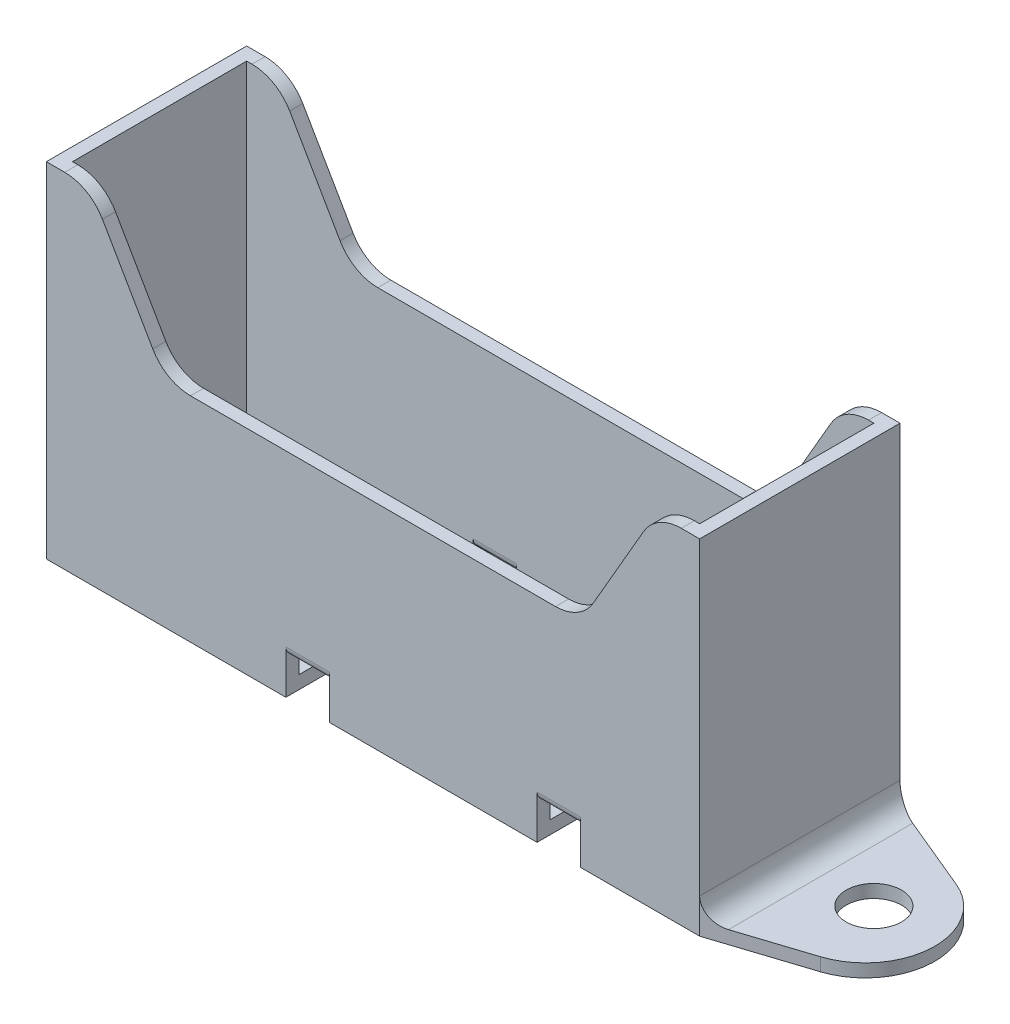
SolidWorks part; units mm, degrees
ref_plane "Front Plane" through (0, 0, 0) normal (0, 0, 1) x (1, 0, 0)
ref_plane "Top Plane" through (0, 0, 0) normal (0, 1, 0) x (1, 0, 0)
ref_plane "Right Plane" through (0, 0, 0) normal (1, 0, 0) x (0, 0, -1)
sketch "Sketch15" plane through (0, 0, 0) normal (0, 1, 0) x (1, 0, 0)
  line L0 (-37.5, -11.5) -> (-37.5, 11.5)
  line L1 (-36, -10) -> (36, -10)
  line L2 (-36, -10) -> (-36, 10)
  line L3 (-36, 10) -> (36, 10)
  line L4 (36, -10) -> (36, 10)
  line L5 (-36, -10) -> (36, 10) construction
  line L6 (-36, 10) -> (36, -10) construction
  line L7 (-37.5, 11.5) -> (37.5, 11.5)
  line L8 (37.5, -11.5) -> (37.5, 11.5)
  line L9 (-37.5, -11.5) -> (37.5, -11.5)
  point P0 (0, 0)
  dimension "D1" = 72
  dimension "D2" = 20
  dimension "D3" = 1.5
extrude "Boss-Extrude8" add sketch "Sketch15" along normal blind 38
sketch "Sketch18" plane through (0, 0, 0) normal (0, -1, 0) x (1, 0, 0)
  line L0 (-37.5, 11.5) -> (37.5, 11.5)
  line L1 (37.5, 11.5) -> (47.9649, 8.1108)
  line L2 (48.5769, -6.8846) -> (37.5, -11.5)
  line L3 (37.5, 11.5) -> (37.5, -11.5) construction
  line L4 (37.5, -11.5) -> (-11.3547, -11.5)
  line L8 (-37.5, 11.5) -> (-37.5, -11.5)
  line L10 (-23.3548, 19.5) -> (-23.3548, -0.3951) construction
  line L12 (-11.3547, -11.5) -> (-15.9702, -22.5769)
  line L13 (-35.3548, -11.5) -> (-30.7394, -22.5769)
  line L14 (-35.3548, -11.5) -> (-37.5, -11.5)
  line L15 (-23.3548, -19.5) -> (1.0726, 24.9274) construction
  line L16 (1.0726, 24.9274) -> (45.5, 0.5) construction
  line L17 (-23.3548, -19.5) -> (45.5, 0.5) construction
  arc A0 (47.9649, 8.1108) -> (48.5769, -6.8846) centre (45.5, 0.5) cw
  arc A3 (-15.9702, -22.5769) -> (-30.7394, -22.5769) centre (-23.3548, -19.5) cw
  dimension "D1" = 8
  dimension "D4" = 90
  dimension "D8" = 8
  dimension "D2" = 8
  dimension "D3" = 67.38
  dimension "D5" = 50.7
  dimension "D6" = 50.7
  dimension "D9" = 8
  dimension "D10" = 67.38
extrude "Boss-Extrude11" add sketch "Sketch18" along normal blind 1.5
hole_wizard "1/4 (0.25) Diameter Hole1" positions "Sketch19" profile "Sketch20" hole size "1/4" standard "ANSI Inch" end condition through all
sketch "Sketch19" plane through (0, 0, 0) normal (0, 1, 0) x (1, 0, 0)
  point P8 (46, 0)
  point P10 (46, 0)
  point P21 (-23.3548, 19.5)
sketch "Sketch20" plane through (46, 0, 0) normal (1, 0, 0) x (0, 0, 1)
  line L0 (0, 0) -> (0, 1.5)
  line L1 (0, 1.5) -> (3.175, 1.5)
  line L2 (3.175, 1.5) -> (3.175, 0)
  line L5 (3.175, 0) -> (0, 0)
  line L11 (0, -6.35) -> (0, 107.95) construction
  dimension "Thru Hole Dia." = 6.35
  dimension "Thru Hole Depth" = 1.5
sketch "Sketch21" plane through (0, 0, -11.5) normal (0, 0, -1) x (-1, 0, 0)
  line L0 (0, -4.7141) -> (0, 50.0572) construction
  line L1 (-32.5, 38) -> (-23.8397, 23)
  line L2 (-37.5, 38) -> (37.5, 38) construction
  line L3 (-23.8397, 23) -> (23.8397, 23)
  line L4 (23.8397, 23) -> (32.5, 38)
  line L5 (32.5, 38) -> (-32.5, 38)
  line L6 (11.3547, -1.5) -> (-37.5, -1.5) construction
  line L7 (-23.8397, -1.5) -> (-18.8397, -1.5)
  line L8 (-23.8397, -1.5) -> (-23.8397, 2.5)
  line L9 (-23.8397, 2.5) -> (-18.8397, 2.5)
  line L10 (-18.8397, -1.5) -> (-18.8397, 2.5)
  line L12 (5, -1.5) -> (10, -1.5)
  line L13 (5, -1.5) -> (5, 2.5)
  line L14 (5, 2.5) -> (10, 2.5)
  line L15 (10, -1.5) -> (10, 2.5)
  dimension "D1" = 60
  dimension "D2" = 5
  dimension "D3" = 15
  dimension "D4" = 5
  dimension "D5" = 5
  dimension "D6" = 5
  dimension "D7" = 4
extrude "Cut-Extrude1" cut sketch "Sketch21" against normal through all
fillet "Fillet1" radius 5 8 edges at (-32.5, 38, 10.75) (32.5, 38, 10.75) (-32.5, 38, -10.75) (-23.8397, 23, -10.75) (-23.8397, 23, 10.75) (23.8397, 23, 10.75) (32.5, 38, -10.75) (23.8397, 23, -10.75)
fillet "Fillet2" radius 1 8 edges at (21.3397, 2.5, -11.5) (21.3397, 2.5, -10) (21.3397, 2.5, 10) (21.3397, 2.5, 11.5) (-7.5, 2.5, -11.5) (-7.5, 2.5, -10) (-7.5, 2.5, 10) (-7.5, 2.5, 11.5)
fillet "Fillet3" radius 2.5 2 edges at (37.5, 0, 0) (-23.3548, 0, -11.5)
